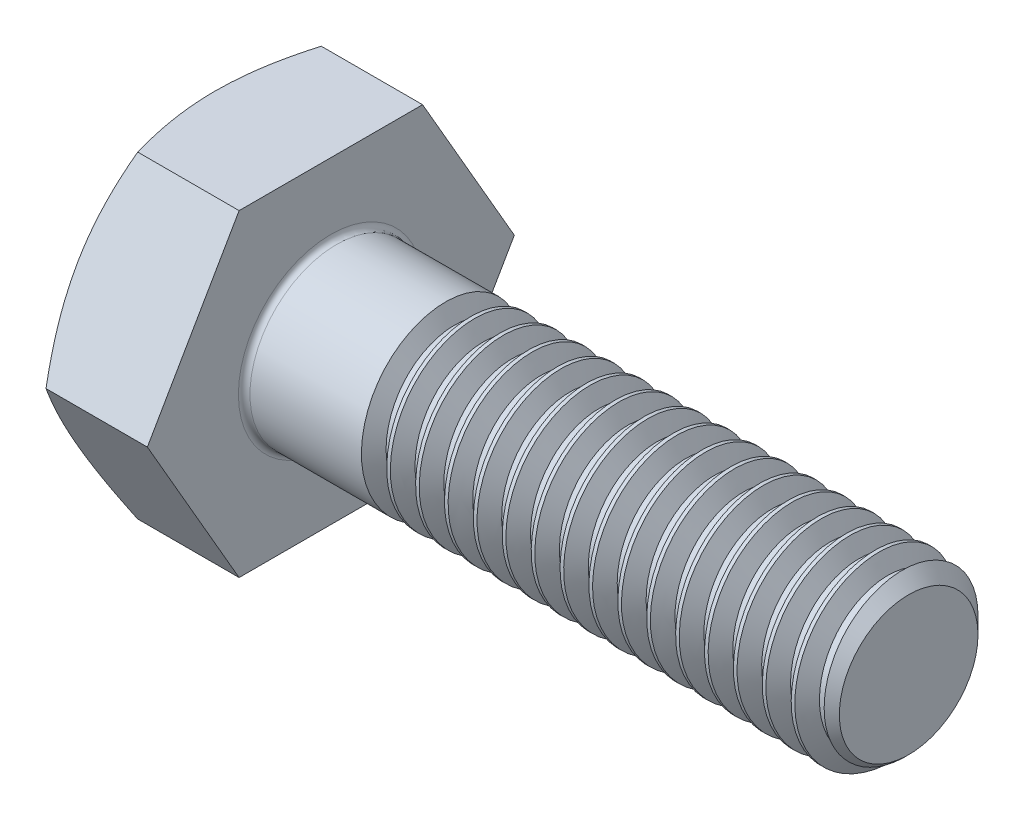
SolidWorks part; units mm, degrees
ref_plane "前视基准面" through (0, 0, 0) normal (0, 0, 1) x (1, 0, 0)
ref_plane "上视基准面" through (0, 0, 0) normal (0, 1, 0) x (1, 0, 0)
ref_plane "右视基准面" through (0, 0, 0) normal (1, 0, 0) x (0, 0, -1)
sketch "草图1" plane through (0, 0, 0) normal (1, 0, 0) x (0, 0, -1)
  line L1 (3.1754, 0) -> (1.5877, 2.75)
  line L2 (1.5877, 2.75) -> (-1.5877, 2.75)
  line L3 (-1.5877, 2.75) -> (-3.1754, 0)
  line L4 (-3.1754, 0) -> (-1.5877, -2.75)
  line L5 (-1.5877, -2.75) -> (1.5877, -2.75)
  line L6 (1.5877, -2.75) -> (3.1754, 0)
  circle A0 centre (0, 0) radius 2.75 construction
  dimension "D1" = 5.5
extrude "拉伸1" add sketch "草图1" along normal blind 2
sketch "草图2" plane through (0, 0, 0) normal (-1, 0, 0) x (0, 0, 1)
  circle A0 centre (0, 0) radius 2.75
  dimension "D1" = 5.5
sketch "草图3" plane through (0, 0, 0) normal (0, 1, 0) x (1, 0, 0)
  line L0 (-18.0603, 0) -> (41.5769, 0) construction
  line L1 (0, 2.75) -> (0.2456, 3.1754)
  line L2 (0, 2.75) -> (0, -2.75)
  line L3 (0, 2.75) -> (0, -2.75)
  line L4 (2, 3.1754) -> (0, 3.1754) construction
  line L5 (0, 2.75) -> (0, 3.1754)
  line L6 (0, 3.1754) -> (0.2456, 3.1754)
  dimension "D2" = 30
  dimension "D1" = 0
revolve "切除-旋转2" cut sketch "草图3" angle 360 about L0
sketch "草图4" plane through (2, 0, 0) normal (1, 0, 0) x (0, 0, -1)
  circle A0 centre (0, 0) radius 1.5
  dimension "D1" = 3
extrude "拉伸2" add sketch "草图4" along normal blind 10
chamfer "倒角1" distance 0.3 angle 45 1 edges at (12, 0, -1.5)
sketch "草图5" plane through (0, 0, 0) normal (0, 1, 0) x (1, 0, 0)
  line L0 (217.2267, 1.5) -> (226.9644, 1.5) construction
  line L1 (11.7, 1.5) -> (2, 1.5) construction
  line L2 (12, 12.6777) -> (12, 22.4507) construction
  line L3 (12, -1.2) -> (12, 1.2) construction
  line L4 (11.9375, 1.2294) -> (11.7812, 1.5)
  line L5 (12.0625, 1.2294) -> (12.2187, 1.5)
  line L6 (11.7812, 1.5) -> (12.2187, 1.5)
  line L7 (11.9375, 1.2294) -> (12.0625, 1.2294)
  dimension "D1" = 30
  dimension "D2" = 30
  dimension "D3" = 0.4375
  dimension "D4" = 0.125
sketch "草图6" plane through (12, 0, 0) normal (1, 0, 0) x (0, 0, -1)
  circle A0 centre (0, 0) radius 1.5
  dimension "D1" = 3
curve "螺旋线1" pitch 0.5 height 8 radius 1.5 centre (12, 0, 0) axis (-1, 0, 0) start towards (0, 0, -1)
sweep "切除-扫描1" cut profiles "草图5" path "螺旋线1"
fillet "圆角1" radius 0.1 1 edges at (2, 0, -1.5) type face fillet first side face at (2, 0, -1.5) second side face at (2, 0, 0)
